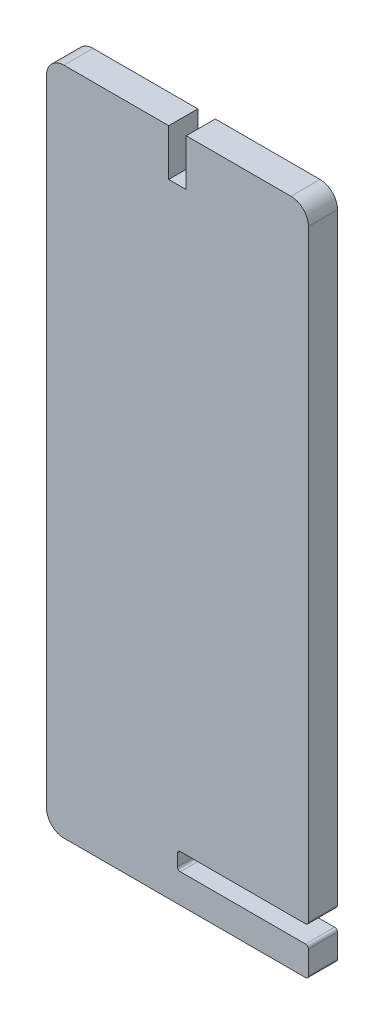
SolidWorks part; units mm, degrees
ref_plane "Alzado" through (0, 0, 0) normal (0, 0, 1) x (1, 0, 0)
ref_plane "Planta" through (0, 0, 0) normal (0, 1, 0) x (1, 0, 0)
ref_plane "Vista lateral" through (0, 0, 0) normal (1, 0, 0) x (0, 0, -1)
sketch "Croquis1" plane through (0, 0, 0) normal (0, 0, 1) x (1, 0, 0)
  line L1 (-22.5, 45) -> (22.5, 45)
  line L2 (-22.5, 45) -> (-22.5, -70)
  line L3 (-22.5, -70) -> (22.5, -70)
  line L4 (22.5, 45) -> (22.5, -70)
  dimension "D1" = 45
  dimension "D2" = 22.5
  dimension "D3" = 115
  dimension "D4" = 45
extrude "Saliente-Extruir1" add sketch "Croquis1" along normal blind 5 contours L2 L3 L4 L1
sketch "Croquis3" plane through (0, 0, 5) normal (0, 0, 1) x (1, 0, 0)
  line L0 (22.5, 45) -> (22.5, -70) construction
  line L1 (22.5, -62) -> (0, -62)
  line L2 (22.5, -62) -> (22.5, -65)
  line L3 (22.5, -65) -> (0, -65)
  line L4 (0, -62) -> (0, -65)
  line L5 (-22.5, -70) -> (22.5, -70) construction
  dimension "D1" = 3
  dimension "D2" = 5
  dimension "D3" = 22.5
extrude "Cortar-Extruir2" cut sketch "Croquis3" against normal up to surface (5 mm away) up to face at (0, -12.5, 0)
fillet "Redondeo1" radius 3 3 edges at (-22.5, -70, 2.5) (22.5, 45, 2.5) (-22.5, 45, 2.5)
sketch "Croquis4" plane through (0, 0, 5) normal (0, 0, 1) x (1, 0, 0)
  line L5 (0, 0) -> (0, 53.685) construction
  line L6 (-19.5, 45) -> (19.5, 45) construction
  line L7 (-1.5, 45) -> (1.5, 45)
  line L8 (-1.5, 45) -> (-1.5, 37)
  line L9 (-1.5, 37) -> (1.5, 37)
  line L10 (1.5, 45) -> (1.5, 37)
  dimension "D1" = 1.5
  dimension "D2" = 1.5
  dimension "D3" = 8
extrude "Cortar-Extruir3" cut sketch "Croquis4" against normal up to surface (5 mm away) up to face at (2.2617, -26.0344, 0)
fillet "Redondeo2" radius 0.5 5 edges at (0, -62, 2.5) (0, -65, 2.5) (22.5, -70, 2.5) (22.5, -65, 2.5) (22.5, -62, 2.5)
